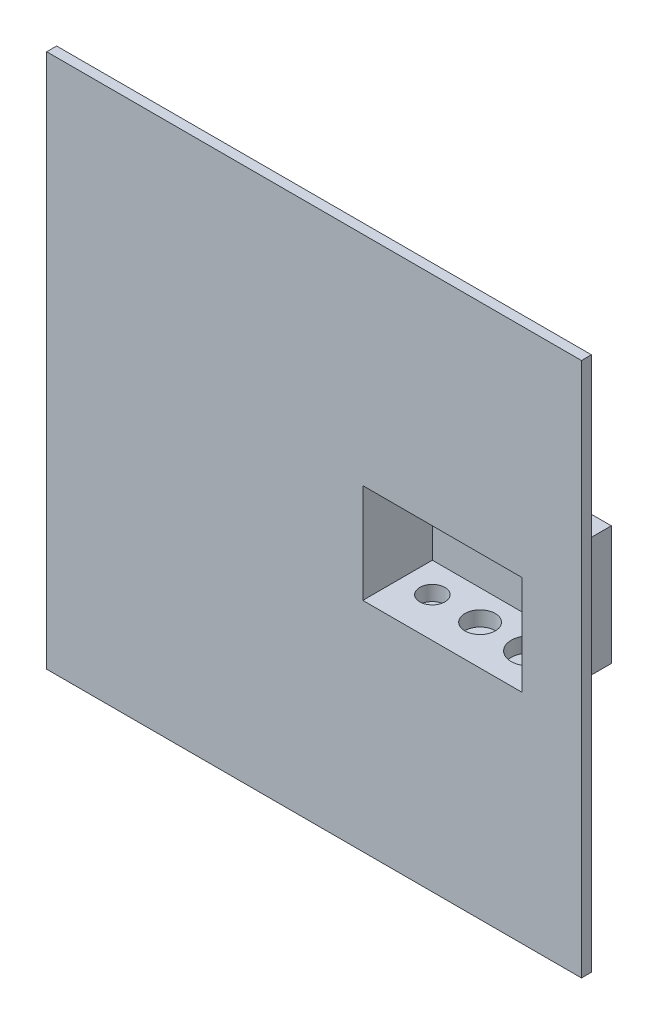
SolidWorks part; units mm, degrees
material "Oak"
ref_plane "Front Plane" through (0, 0, 0) normal (0, 0, 1) x (1, 0, 0)
ref_plane "Top Plane" through (0, 0, 0) normal (0, 1, 0) x (1, 0, 0)
ref_plane "Right Plane" through (0, 0, 0) normal (1, 0, 0) x (0, 0, -1)
sketch "Sketch1" plane through (0, 0, 0) normal (0, 0, 1) x (1, 0, 0)
  line L1 (0, 0) -> (683.26, 0)
  line L2 (0, 0) -> (0, 683.26)
  line L3 (0, 683.26) -> (683.26, 683.26)
  line L4 (683.26, 0) -> (683.26, 683.26)
  line L5 (403.86, 405.13) -> (607.06, 405.13)
  line L6 (403.86, 405.13) -> (403.86, 278.13)
  line L7 (403.86, 278.13) -> (607.06, 278.13)
  line L8 (607.06, 405.13) -> (607.06, 278.13)
  point P9 (607.06, 341.63)
  dimension "D1" = 683.26
  dimension "D2" = 76.2
  dimension "D3" = 341.63
  dimension "D4" = 127
  dimension "D5" = 203.2
extrude "Boss-Extrude1" add sketch "Sketch1" along normal blind 12.7
sketch "Sketch2" plane through (0, 278.13, 0) normal (0, 1, 0) x (1, 0, 0)
  line L1 (403.86, 0) -> (607.06, 0)
  line L2 (403.86, 0) -> (403.86, 76.2)
  line L3 (403.86, 76.2) -> (607.06, 76.2)
  line L4 (607.06, 0) -> (607.06, 76.2)
  dimension "D1" = 76.2
extrude "Boss-Extrude2" add sketch "Sketch2" against normal blind 25.4
sketch "Sketch3" plane through (0, 278.13, 0) normal (0, 1, 0) x (1, 0, 0)
  line L6 (607.06, -12.7) -> (607.06, 0)
  line L7 (607.06, 0) -> (607.06, 76.2)
  line L8 (607.06, 76.2) -> (403.86, 76.2)
  line L9 (403.86, 76.2) -> (403.86, 0)
  line L10 (403.86, 0) -> (403.86, -12.7)
  line L11 (403.86, -12.7) -> (607.06, -12.7)
  line L12 (607.06, -12.7) -> (607.06, 0)
  line L13 (607.06, 0) -> (607.06, 76.2)
  line L14 (607.06, 76.2) -> (403.86, 76.2)
  line L15 (403.86, 76.2) -> (403.86, 0)
  line L16 (403.86, 0) -> (403.86, -12.7)
  line L17 (403.86, -12.7) -> (607.06, -12.7)
  circle A1 centre (441.96, 38.1) radius 16.0655
  circle A2 centre (502.92, 38.1) radius 19.3675
  circle A3 centre (566.42, 38.1) radius 23.6855
  point P6 (403.86, 38.1)
  dimension "D2" = 32.131
  dimension "D4" = 38.735
  dimension "D5" = 47.371
  dimension "D3" = 38.1
  dimension "D6" = 60.96
  dimension "D7" = 63.5
  dimension "D1" = 0
extrude "Cut-Extrude1" cut sketch "Sketch3" against normal blind 19.05 contours A3 | A2 | A1 region at (441.96, 278.13, -38.1) region at (502.92, 278.13, -38.1) region at (566.42, 278.13, -38.1)
sketch "Sketch4" plane through (0, 0, 0) normal (0, 0, -1) x (-1, 0, 0)
  line L0 (-607.06, 278.13) -> (-403.86, 278.13) construction
  line L1 (-607.06, 278.13) -> (-619.76, 278.13)
  line L2 (-607.06, 278.13) -> (-607.06, 405.13)
  line L3 (-607.06, 405.13) -> (-619.76, 405.13)
  line L4 (-619.76, 278.13) -> (-619.76, 405.13)
  line L5 (-607.06, 405.13) -> (-403.86, 405.13)
  line L6 (-607.06, 405.13) -> (-607.06, 417.83)
  line L7 (-607.06, 417.83) -> (-403.86, 417.83)
  line L8 (-403.86, 405.13) -> (-403.86, 417.83)
  line L9 (-403.86, 405.13) -> (-391.16, 405.13)
  line L10 (-403.86, 405.13) -> (-403.86, 278.13)
  line L11 (-403.86, 278.13) -> (-391.16, 278.13)
  line L12 (-391.16, 405.13) -> (-391.16, 278.13)
  line L13 (-403.86, 405.13) -> (-403.86, 278.13) construction
  line L15 (-607.06, 405.13) -> (-403.86, 405.13) construction
  line L16 (-607.06, 405.13) -> (-619.76, 405.13)
  line L17 (-607.06, 405.13) -> (-607.06, 417.83)
  line L18 (-607.06, 417.83) -> (-619.76, 417.83)
  line L19 (-619.76, 405.13) -> (-619.76, 417.83)
  line L20 (-403.86, 405.13) -> (-391.16, 405.13)
  line L21 (-403.86, 405.13) -> (-403.86, 417.83)
  line L22 (-403.86, 417.83) -> (-391.16, 417.83)
  line L23 (-391.16, 405.13) -> (-391.16, 417.83)
  line L24 (-607.06, 278.13) -> (-619.76, 278.13)
  line L25 (-607.06, 278.13) -> (-607.06, 265.43)
  line L26 (-607.06, 265.43) -> (-619.76, 265.43)
  line L27 (-619.76, 278.13) -> (-619.76, 265.43)
  line L28 (-403.86, 278.13) -> (-391.16, 278.13)
  line L29 (-403.86, 278.13) -> (-403.86, 265.43)
  line L30 (-403.86, 265.43) -> (-391.16, 265.43)
  line L31 (-391.16, 278.13) -> (-391.16, 265.43)
  line M7 (-403.86, 278.13) -> (-403.86, 252.73)
  line M9 (-607.06, 252.73) -> (-607.06, 278.13)
  line M10 (-607.06, 278.13) -> (-607.06, 405.13)
  line M11 (-607.06, 405.13) -> (-403.86, 405.13)
  line M12 (-403.86, 405.13) -> (-403.86, 278.13)
  dimension "D1" = 12.7
  dimension "D2" = 12.7
  dimension "D3" = 12.7
extrude "Boss-Extrude4" add sketch "Sketch4" along normal up to surface (76.2 mm away) contours L1 L27 L26 M9 | L4 L1 L3 M10 | L8 L7 L6 M11 | L19 L3 L6 L18 | L9 L23 L22 L8 | L12 L9 L11 M12 | L31 L11 L30 M7 region at (613.41, 271.78, 0) region at (613.41, 341.63, 0) region at (505.46, 411.48, 0) region at (613.41, 411.48, 0) region at (397.51, 411.48, 0) region at (397.51, 341.63, 0) region at (397.51, 271.78, 0) up to face at (505.46, 265.43, -76.2)
sketch "Sketch5" plane through (0, 0, -76.2) normal (0, 0, -1) x (-1, 0, 0)
  line L4 (-607.06, 252.73) -> (-403.86, 252.73)
  line L5 (-391.16, 265.43) -> (-391.16, 417.83)
  line L6 (-391.16, 417.83) -> (-619.76, 417.83)
  line L7 (-619.76, 417.83) -> (-619.76, 265.43)
  line L8 (-607.06, 252.73) -> (-403.86, 252.73)
  line L9 (-391.16, 265.43) -> (-391.16, 417.83)
  line L10 (-391.16, 417.83) -> (-619.76, 417.83)
  line L11 (-619.76, 417.83) -> (-619.76, 265.43)
  line L16 (-403.86, 252.73) -> (-403.86, 265.43)
  line L17 (-403.86, 252.73) -> (-403.86, 265.43)
  line L18 (-403.86, 265.43) -> (-391.16, 265.43)
  line L19 (-403.86, 265.43) -> (-391.16, 265.43)
  line L20 (-619.76, 265.43) -> (-607.06, 265.43)
  line L21 (-619.76, 265.43) -> (-607.06, 265.43)
  line L22 (-607.06, 265.43) -> (-607.06, 252.73)
  line L23 (-607.06, 265.43) -> (-607.06, 252.73)
  dimension "D1" = 0
extrude "Boss-Extrude5" add sketch "Sketch5" along normal blind 12.7
